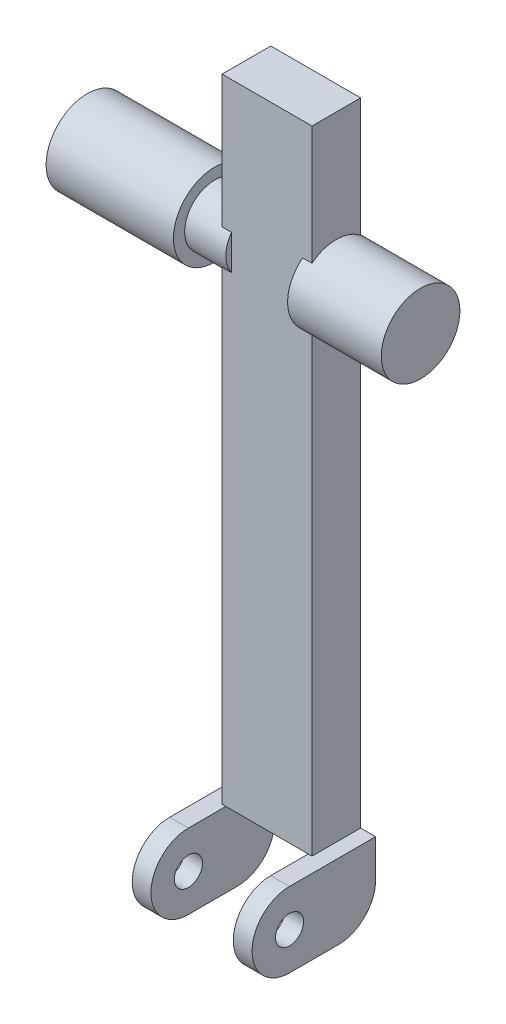
SolidWorks part; units mm, degrees
ref_plane "Front Plane" through (0, 0, 0) normal (0, 0, 1) x (1, 0, 0)
ref_plane "Top Plane" through (0, 0, 0) normal (0, 1, 0) x (1, 0, 0)
ref_plane "Right Plane" through (0, 0, 0) normal (1, 0, 0) x (0, 0, -1)
sketch "Sketch1" plane through (0, 0, 0) normal (0, 1, 0) x (1, 0, 0)
  line L1 (-24, 13) -> (24, 13)
  line L2 (-24, 13) -> (-24, -13)
  line L3 (-24, -13) -> (24, -13)
  line L4 (24, 13) -> (24, -13)
  line L5 (-24, 13) -> (24, -13) construction
  line L6 (-24, -13) -> (24, 13) construction
  point P0 (0, 0)
ref_plane "Plane1" through (19, 0, 0) normal (1, 0, 0) x (0, 0, -1)
sketch "Sketch2" plane through (19, 0, 0) normal (1, 0, 0) x (0, 0, -1)
  line L0 (13, 0) -> (-13, 0) construction
  circle A0 centre (0, 0) radius 21
ref_plane "Plane2" through (-19, 0, 0) normal (1, 0, 0) x (0, 0, -1)
sketch "Sketch3" plane through (-19, 0, 0) normal (1, 0, 0) x (0, 0, -1)
  line L0 (13, 0) -> (-13, 0) construction
  circle A0 centre (0, 0) radius 16
extrude "Boss-Extrude1" add sketch "Sketch3" against normal blind 22
ref_plane "Plane3" through (-41, 0, 0) normal (-1, 0, 0) x (0, 0, 1)
sketch "Sketch4" plane through (-41, 0, 0) normal (-1, 0, 0) x (0, 0, 1)
  circle A0 centre (0, 0) radius 22
extrude "Boss-Extrude2" add sketch "Sketch4" along normal blind 68
extrude "Boss-Extrude3" add sketch "Sketch2" along normal blind 50 separate body
extrude "Boss-Extrude5" add sketch "Sketch1" along normal blind 80 and the other way blind 257.72
ref_plane "Plane4" through (24, 0, 0) normal (1, 0, 0) x (0, 0, -1)
sketch "Sketch5" plane through (24, 0, 0) normal (1, 0, 0) x (0, 0, -1)
  line L1 (13, -257.72) -> (-33, -257.72)
  line L3 (13, -257.72) -> (13, -277.72)
  line L4 (-7, -297.72) -> (-33, -297.72)
  line L5 (-13, -257.72) -> (13, -257.72) construction
  arc A0 (-33, -257.72) -> (-33, -297.72) centre (-33, -277.72) ccw
  arc A1 (-7, -297.72) -> (13, -277.72) centre (-7, -277.72) ccw
  dimension "D1" = 20
  dimension "D2" = 20
  dimension "D3" = 20
  dimension "D4" = 46
extrude "Boss-Extrude7" add sketch "Sketch5" along normal blind 8 and the other way blind 2 separate body
ref_plane "Plane8" through (22, 0, 0) normal (-1, 0, 0) x (0, 0, 1)
sketch "Sketch10" plane through (22, 0, 0) normal (-1, 0, 0) x (0, 0, 1)
  circle A0 centre (33, -277.72) radius 7.5
extrude "Cut-Extrude4" cut sketch "Sketch10" against normal up to vertex (10 mm away) up to point (32, -297.72, 33)
mirror "Mirror26" about plane through (0, 0, 0) normal (1, 0, 0) of "Cut-Extrude4", "Boss-Extrude7"
ref_point "Point1"
ref_point "Point2"
ref_axis "Axis1" through (69, 0, 0) along (-1, 0, 0)
sketch "Sketch11" plane through (-109, 0, 0) normal (-1, 0, 0) x (0, 0, 1)
  line L0 (0, 0) -> (0, 22) construction
  circle A0 centre (0, 0) radius 22 construction
ref_plane "Plane5" through (0, 0, 0) normal (1, 0, 0) x (0, 0, -1)
ref_plane "Plane9" through (0, 0, 0) normal (0, 1, 0) x (1, 0, 0)
ref_plane "Plane10" through (0, 0, 0) normal (0, 0, -1) x (-1, 0, 0)
ref_axis "Axis2" through (0, 0, 52.1997) along (0, 0, -1)
ref_axis "Axis3" through (0, 186.9, 0) along (0, -1, 0)
ref_point "Point3"
ref_point "Point4"
ref_axis "Axis4" through (132.7947, -277.72, 33) along (-1, 0, 0)
ref_plane "Plane11" through (0, 0, 0) normal (0, -0.118, -0.993) x (-1, 0, 0)
ref_axis "Axis5" through (0, 14.9554, -1.7771) along (0, -0.993, 0.118)
